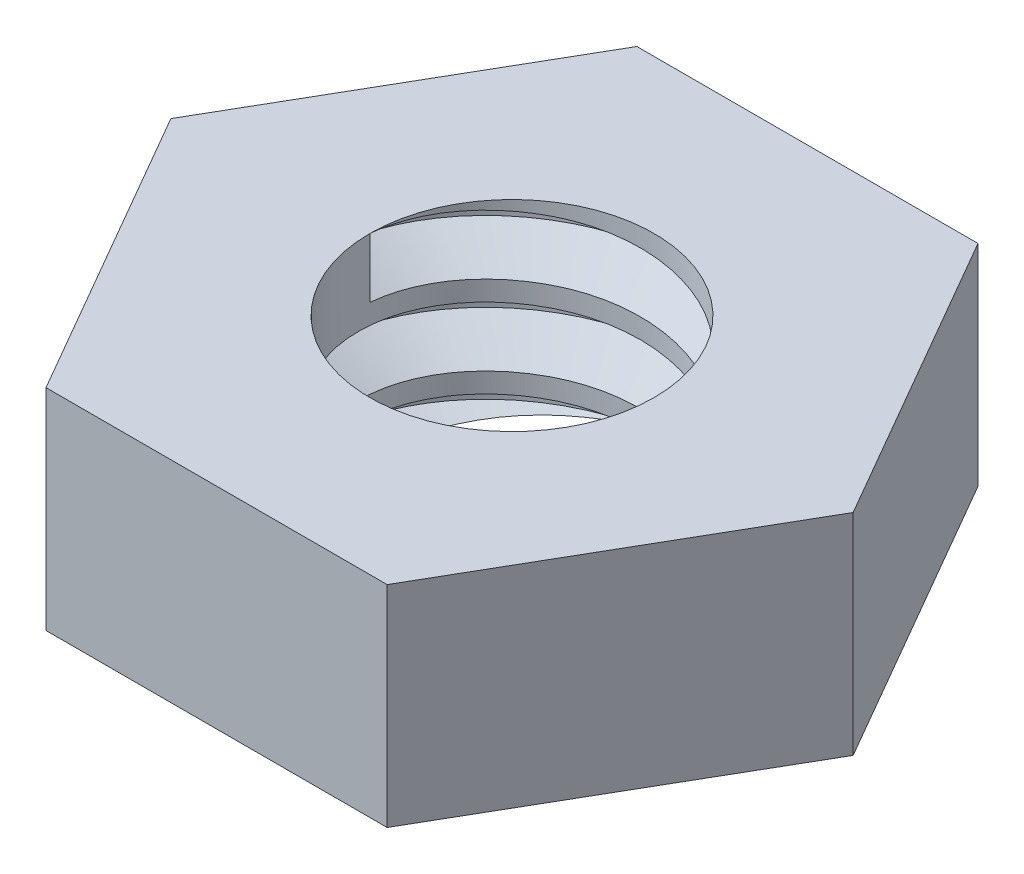
SolidWorks part; units mm, degrees
ref_plane "Front" through (0, 0, 0) normal (0, 0, 1) x (1, 0, 0)
ref_plane "Top" through (0, 0, 0) normal (0, 1, 0) x (1, 0, 0)
ref_plane "Right" through (0, 0, 0) normal (1, 0, 0) x (0, 0, -1)
sketch "Sketch1" plane through (0, 0, 0) normal (0, 1, 0) x (1, 0, 0)
  line L1 (3, 0) -> (1.5, 2.5981)
  line L2 (1.5, 2.5981) -> (-1.5, 2.5981)
  line L3 (-1.5, 2.5981) -> (-3, 0)
  line L4 (-3, 0) -> (-1.5, -2.5981)
  line L5 (-1.5, -2.5981) -> (1.5, -2.5981)
  line L6 (1.5, -2.5981) -> (3, 0)
  circle A0 centre (0, 0) radius 2.5981 construction
  dimension "D1" = 3
extrude "Boss-Extrude1" add sketch "Sketch1" along normal blind 1.85
sketch "Sketch2" plane through (0, 1.85, 0) normal (0, 1, 0) x (1, 0, 0)
  circle A0 centre (0, 0) radius 1.25
  dimension "D1" = 2.5
extrude "Cut-Extrude1" cut sketch "Sketch2" against normal blind 1.85
thread "Thread1" pitch 0.7 method cut profile "Thread Profile1" start angle 0, offset 0, length 11, pitch 0.7, diameter 2.5
ref_plane "Plane1" through (-1.25, 1.85, 0) normal (0, 0, 1) x (-1, 0, 0)
sketch "Thread Profile1" plane through (-1.25, 1.85, 0) normal (0, 0, 1) x (-1, 0, 0)
  line L0 (0, 0) -> (0, 0.7) construction
  line L1 (0, 0) -> (0.3789, 0.2187)
  line L2 (0.3789, 0.2187) -> (0.3789, 0.3062)
  line L3 (0.3789, 0.3062) -> (0, 0.525)
  line L4 (0.3789, 0.2625) -> (0, 0.2625) construction
  line L11 (0, 0) -> (0, 0.525)
  point P2 (0, 0)
  dimension "Pitch" = 0.7
  dimension "Profile_Angle" = 60
  dimension "Profile_Land" = 0.0875
  dimension "Profile_Height" = 0.3789
